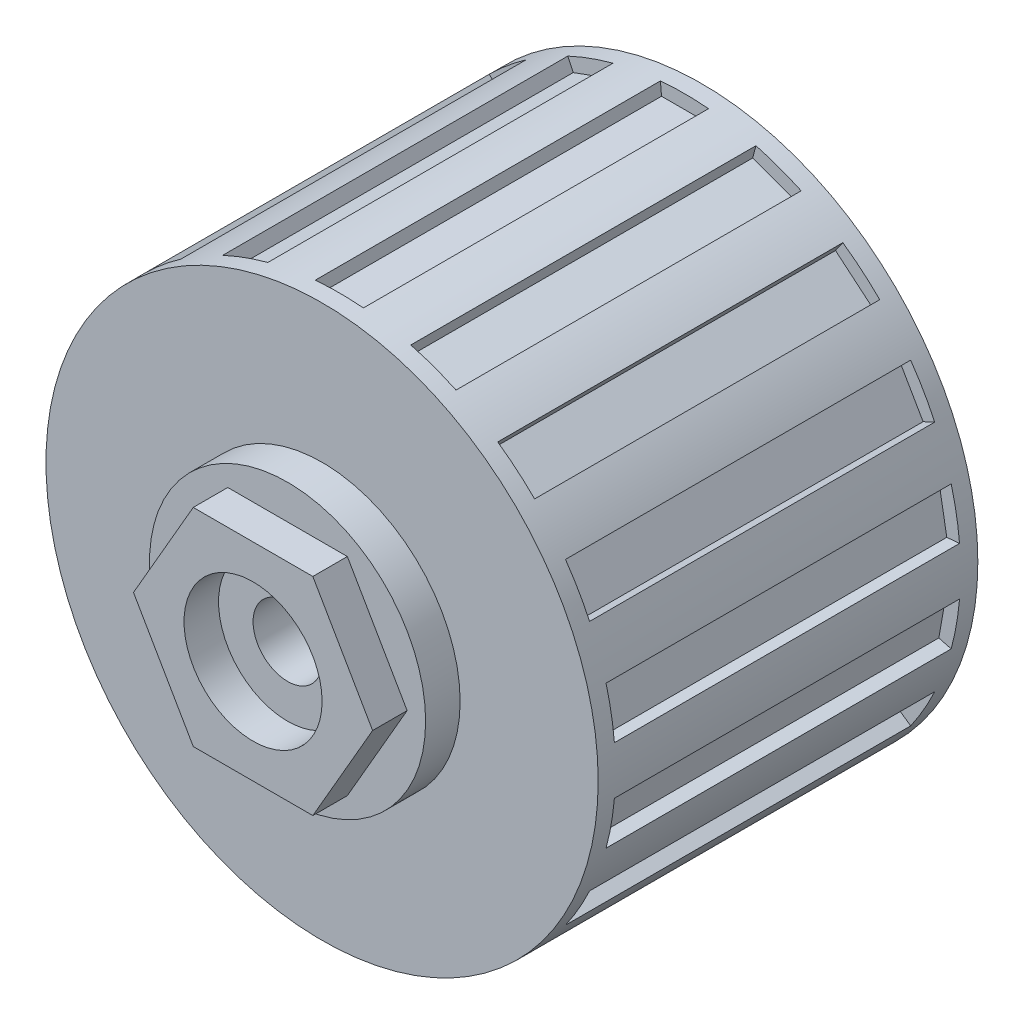
SolidWorks part; units mm, degrees
ref_plane "前视基准面" through (0, 0, 0) normal (0, 0, 1) x (1, 0, 0)
ref_plane "上视基准面" through (0, 0, 0) normal (0, 1, 0) x (1, 0, 0)
ref_plane "右视基准面" through (0, 0, 0) normal (1, 0, 0) x (0, 0, -1)
sketch "草图1" plane through (0, 0, 0) normal (0, 0, 1) x (1, 0, 0)
  circle A0 centre (0, 0) radius 80
  circle A1 centre (0, 0) radius 10
  dimension "D1" = 160
  dimension "D2" = 20
extrude "凸台-拉伸1" add sketch "草图1" along normal blind 120
ref_plane "基准面1" through (0, 0, 105) normal (0, 0, 1) x (1, 0, 0)
sketch "草图2" plane through (0, 0, 105) normal (0, 0, 1) x (1, 0, 0)
  line L0 (-6.6491, 76) -> (-6.9725, 79.6956)
  line L1 (6.6491, 76) -> (6.9725, 79.6956)
  line L2 (0, 80) -> (0, 76) construction
  line L3 (-6.6491, 76) -> (6.6491, 76)
  circle A0 centre (0, 0) radius 80 construction
  arc A1 (6.9725, 79.6956) -> (-6.9725, 79.6956) centre (0, 0) ccw
  dimension "D1" = 5
  dimension "D2" = 5
  dimension "D3" = 4
extrude "切除-拉伸1" cut sketch "草图2" against normal blind 100
pattern_circular "阵列(圆周)1" count 18 over 360 about axis through (0, 0, 120) along (0, 0, -1) of "切除-拉伸1"
sketch "草图3" plane through (0, 0, 120) normal (0, 0, 1) x (1, 0, 0)
  circle A0 centre (0, 0) radius 50
  circle A1 centre (0, 0) radius 20
  dimension "D1" = 40
extrude "凸台-拉伸2" add sketch "草图3" against normal blind 3
sketch "草图4" plane through (0, 0, 120) normal (0, 0, 1) x (1, 0, 0)
  line L1 (34.641, 0) -> (17.3205, 30)
  line L2 (17.3205, 30) -> (-17.3205, 30)
  line L3 (-17.3205, 30) -> (-34.641, 0)
  line L4 (-34.641, 0) -> (-17.3205, -30)
  line L5 (-17.3205, -30) -> (17.3205, -30)
  line L6 (17.3205, -30) -> (34.641, 0)
  circle A0 centre (0, 0) radius 30 construction
  circle A1 centre (0, 0) radius 20
  dimension "D1" = 60
extrude "凸台-拉伸3" add sketch "草图4" along normal blind 10
sketch "草图5" plane through (0, 0, 120) normal (0, 0, 1) x (1, 0, 0)
  circle A0 centre (0, 0) radius 40
  dimension "D1" = 80
extrude "切除-拉伸2" cut sketch "草图5" against normal blind 10 flip side to cut
sketch "草图6" plane through (0, 0, 0) normal (0, 0, -1) x (-1, 0, 0)
  circle A0 centre (0, 0) radius 40
  circle A1 centre (0, 0) radius 10
  dimension "D1" = 80
  dimension "D2" = 20
extrude "凸台-拉伸4" add sketch "草图6" along normal blind 10
